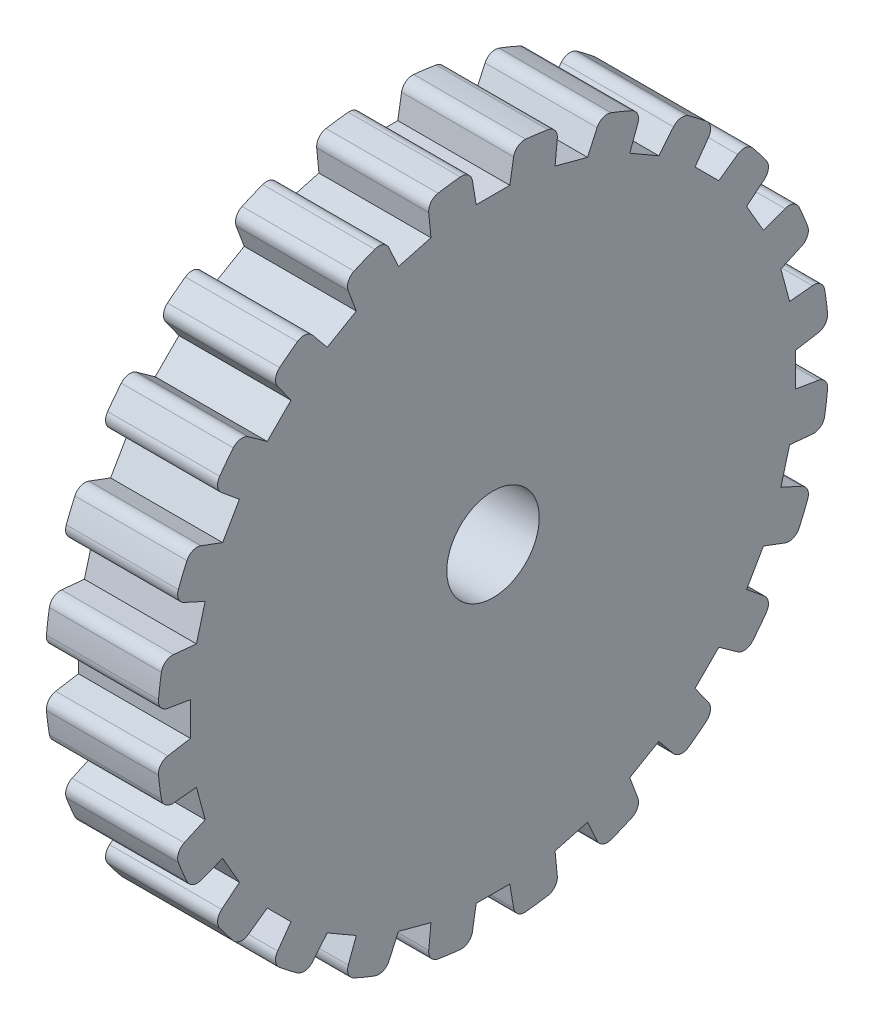
SolidWorks part; units mm, degrees
ref_plane "Front Plane" through (0, 0, 0) normal (0, 0, 1) x (1, 0, 0)
ref_plane "Top Plane" through (0, 0, 0) normal (0, 1, 0) x (1, 0, 0)
ref_plane "Right Plane" through (0, 0, 0) normal (1, 0, 0) x (0, 0, -1)
sketch "Sketch1" plane through (0, 0, 0) normal (0, 0, 1) x (1, 0, 0)
  line L0 (0, 0) -> (-34.486, 0) construction
  line L1 (0, 0) -> (-10, 0)
  line L2 (-10, 0) -> (-10, 5)
  line L3 (-10, 20) -> (-10, 5)
  line L4 (0, 20) -> (0, 5)
  line L6 (-10, 20) -> (-10, 30)
  line L7 (-10, 30) -> (0, 30)
  line L8 (0, 30) -> (0, 20)
  line L12 (0, 5) -> (0, 0)
  dimension "D1" = 30
  dimension "D2" = 30
  dimension "D3" = 10
  dimension "D5" = 5
  dimension "D6" = 10
revolve "Revolve1" add sketch "Sketch1" angle 360 about L0
sketch "Sketch2" plane through (0, 0, 0) normal (1, 0, 0) x (0, 0, -1)
  line L0 (-2.5, 33) -> (2.5, 33)
  line L1 (-1.5, 27) -> (1.5, 27)
  line L2 (-2.5, 33) -> (-1.5, 27)
  line L3 (2.5, 33) -> (1.5, 27)
  circle A0 centre (0, 0) radius 30 construction
  point P0 (0, 0)
  point P3 (0, 30)
  point P7 (0, 30)
  point P8 (0, 27)
  dimension "D1" = 5
  dimension "D2" = 3
  dimension "D3" = 27
extrude "Cut-Extrude1" cut sketch "Sketch2" against normal blind 44
fillet "Fillet1" radius 1 2 edges at (-5, 29.934, -1.989) (-5, 29.934, 1.989)
pattern_circular "CirPattern1" count 24 over 360 about axis through (0, 0, 0) along (1, 0, 0) of "Cut-Extrude1", "Fillet1"
sketch "Sketch4" plane through (-10, 0, 0) normal (-1, 0, 0) x (0, 0, 1)
  circle A0 centre (0, 0) radius 4.125
  point P3 (0, 0)
  point P8 (0, 0)
  dimension "D1" = 8.25
extrude "Cut-Extrude2" cut sketch "Sketch4" against normal blind 10
